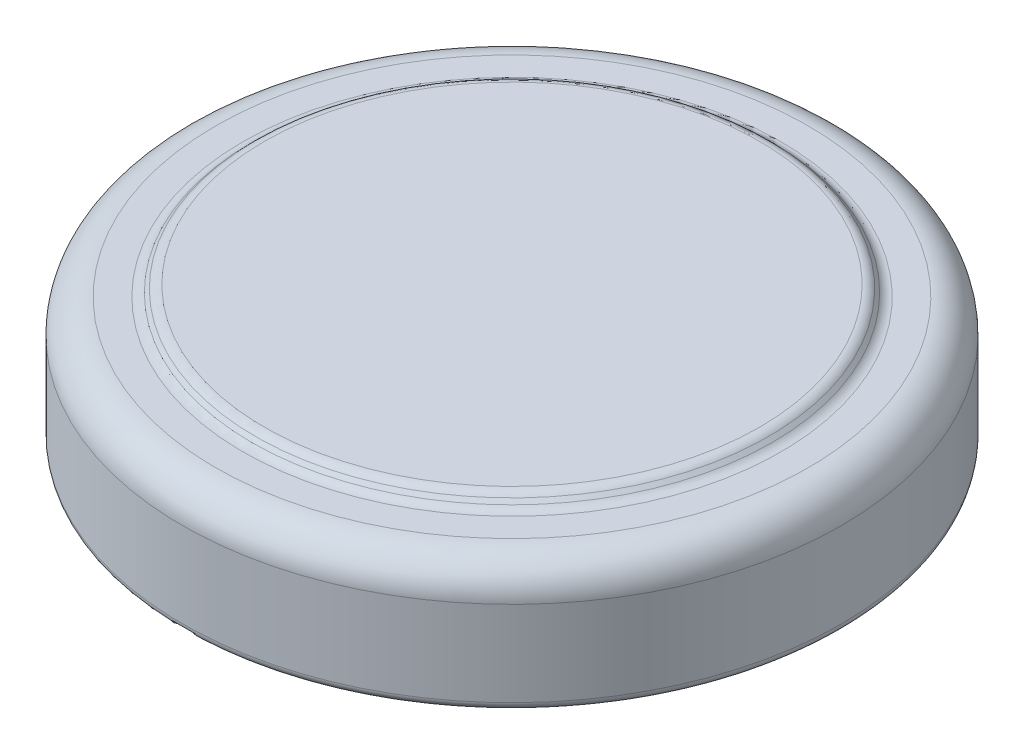
SolidWorks part; units mm, degrees
ref_plane "Front Plane" through (0, 0, 0) normal (0, 0, 1) x (1, 0, 0)
ref_plane "Top Plane" through (0, 0, 0) normal (0, 1, 0) x (1, 0, 0)
ref_plane "Right Plane" through (0, 0, 0) normal (1, 0, 0) x (0, 0, -1)
sketch "Sketch1" plane through (0, 0, 0) normal (0, 0, 1) x (1, 0, 0)
  line L0 (0, 0) -> (-3.85, 0)
  line L1 (-3.95, 0.1) -> (-3.95, 1.12)
  line L2 (-2.9679, 1.65) -> (0, 1.65)
  line L3 (0, 1.65) -> (0, 0)
  line L4 (-3.1161, 1.5639) -> (-3.0739, 1.6061)
  line L7 (-3.2221, 1.52) -> (-3.55, 1.52)
  arc A0 (-3.95, 1.12) -> (-3.55, 1.52) centre (-3.55, 1.12) cw
  arc A1 (-2.9679, 1.65) -> (-3.0739, 1.6061) centre (-2.9679, 1.5) ccw
  arc A2 (-3.2221, 1.52) -> (-3.1161, 1.5639) centre (-3.2221, 1.67) ccw
  arc A3 (-3.85, 0) -> (-3.95, 0.1) centre (-3.85, 0.1) cw
  point P9 (-3.95, 1.52)
  point P13 (-3.16, 1.52)
  point P17 (-3.95, 0)
  point P18 (-3.16, 1.52)
  point P20 (-3.16, 1.52)
  dimension "D6" = 0.4
  dimension "D7" = 0.15
  dimension "D8" = 0.1
  dimension "D1" = 3.95
  dimension "D2" = 1.65
  dimension "D3" = 3.16
  dimension "D4" = 1.52
  dimension "D5" = 45
revolve "Revolve1" add sketch "Sketch1" angle 360 about L3
sketch "Sketch2" plane through (0, 0, 0) normal (0, -1, 0) x (1, 0, 0)
  line L0 (0.25, -0.25) -> (0.25, -1.5)
  line L1 (-0.25, 1.5) -> (0.25, 1.5)
  line L2 (-0.25, 1.5) -> (-0.25, 0.25)
  line L3 (-0.25, -1.5) -> (0.25, -1.5)
  line L4 (0.25, 1.5) -> (0.25, 0.25)
  line L5 (-1.5, 0.25) -> (-0.25, 0.25)
  line L6 (-1.5, 0.25) -> (-1.5, -0.25)
  line L7 (-1.5, -0.25) -> (-0.25, -0.25)
  line L8 (1.5, 0.25) -> (1.5, -0.25)
  line L9 (-0.25, -0.25) -> (-0.25, -1.5)
  line L10 (0.25, 0.25) -> (1.5, 0.25)
  line L11 (0.25, -0.25) -> (1.5, -0.25)
  circle A0 centre (0, 0) radius 2.5 construction
  text T0 "                    SR67" font "Century Gothic" height 1
  dimension "D1" = 5
  dimension "D2" = 0.25
  dimension "D3" = 0.5
  dimension "D4" = 0.25
  dimension "D5" = 0.5
  dimension "D6" = 3
  dimension "D7" = 3
  dimension "D8" = 1.5
  dimension "D9" = 1.5
wrap "Wrap1" sketch "Sketch2" wrap type scribe source sketch "Sketch2" face at (-3.85, 0, 0)
